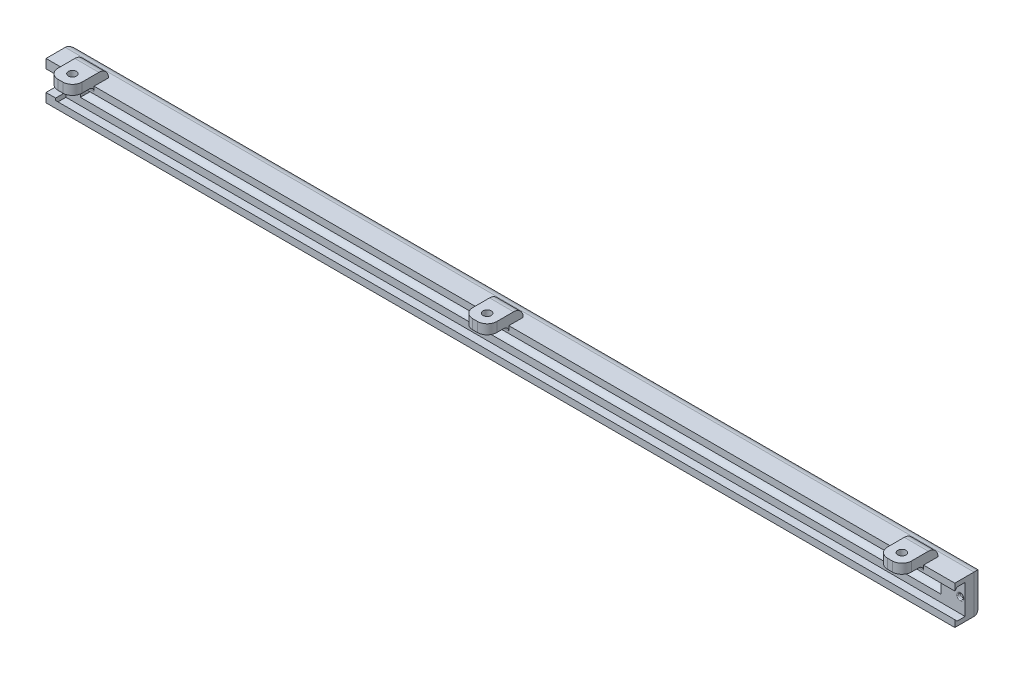
SolidWorks part; units mm, degrees
ref_plane "Front Plane" through (0, 0, 0) normal (0, 0, 1) x (1, 0, 0)
ref_plane "Top Plane" through (0, 0, 0) normal (0, 1, 0) x (1, 0, 0)
ref_plane "Right Plane" through (0, 0, 0) normal (1, 0, 0) x (0, 0, -1)
sketch "Sketch1" plane through (0, 0, 0) normal (0, 0, 1) x (1, 0, 0)
  line L1 (-157.5301, 47.1519) -> (220.4699, 47.1519)
  line L2 (-157.5301, 47.1519) -> (-157.5301, 31.1519)
  line L3 (-157.5301, 31.1519) -> (220.4699, 31.1519)
  line L4 (220.4699, 47.1519) -> (220.4699, 31.1519)
  dimension "D1" = 378
  dimension "D2" = 16
extrude "Boss-Extrude1" add sketch "Sketch1" along normal blind 6
sketch "Sketch3" plane through (220.4699, 0, 0) normal (1, 0, 0) x (0, 0, -1)
  line L0 (-6, 31.1519) -> (-6, 47.1519) construction
  line L1 (-6, 45.3019) -> (-1.7, 45.3019)
  line L2 (-6, 45.3019) -> (-6, 33.0019)
  line L3 (-6, 33.0019) -> (-1.7, 33.0019)
  line L4 (-1.7, 45.3019) -> (-1.7, 33.0019)
  line L5 (-6, 47.1519) -> (0, 47.1519) construction
  dimension "D1" = 12.3
  dimension "D2" = 4.3
  dimension "D3" = 1.85
extrude "Cut-Extrude1" cut sketch "Sketch3" against normal blind 374 and the other way through all
sketch "Sketch4" plane through (220.4699, 0, 0) normal (1, 0, 0) x (0, 0, -1)
  line L0 (-6, 33.0019) -> (-6, 34.0019)
  line L1 (-6, 45.3019) -> (-6, 33.0019) construction
  line L2 (-6, 34.0019) -> (-5, 33.0019)
  line L3 (-6, 33.0019) -> (-1.7, 33.0019) construction
  line L4 (-5, 33.0019) -> (-6, 33.0019)
  dimension "D1" = 1
  dimension "D2" = 1
extrude "Boss-Extrude2" add sketch "Sketch4" against normal blind 374
sketch "Sketch5" plane through (220.4699, 0, 0) normal (1, 0, 0) x (0, 0, -1)
  line L0 (-6, 45.3019) -> (-6, 44.3019)
  line L1 (-6, 45.3019) -> (-6, 34.0019) construction
  line L2 (-6, 44.3019) -> (-5, 45.3019)
  line L3 (-1.7, 45.3019) -> (-6, 45.3019) construction
  line L4 (-5, 45.3019) -> (-6, 45.3019)
  dimension "D1" = 1
  dimension "D2" = 1
extrude "Boss-Extrude3" add sketch "Sketch5" against normal blind 374
sketch "Sketch6" plane through (-153.5301, 0, 0) normal (1, 0, 0) x (0, 0, -1)
  line L0 (-6, 44.3019) -> (-6, 34.0019) construction
  line L1 (-6, 43.4019) -> (-2, 43.4019)
  line L2 (-6, 43.4019) -> (-6, 34.9019)
  line L3 (-6, 34.9019) -> (-2, 34.9019)
  line L4 (-2, 43.4019) -> (-2, 34.9019)
  line L5 (-6, 31.1519) -> (0, 31.1519) construction
  dimension "D1" = 8.5
  dimension "D2" = 3.75
  dimension "D3" = 4
extrude "Cut-Extrude2" cut sketch "Sketch6" against normal through all
sketch "Sketch13" plane through (0, 47.1519, 0) normal (0, 1, 0) x (1, 0, 0)
  line L0 (220.4699, 0) -> (-157.5301, 0) construction
  line L1 (-137.5301, 0) -> (-147.5301, 0)
  line L2 (-137.5301, 0) -> (-137.5301, -15)
  line L3 (-137.5301, -15) -> (-147.5301, -15)
  line L4 (-147.5301, 0) -> (-147.5301, -15)
  line L5 (-157.5301, -6) -> (-157.5301, 0) construction
  dimension "D1" = 10
  dimension "D2" = 10
  dimension "D3" = 15
extrude "Boss-Extrude5" add sketch "Sketch13" along normal blind 4
fillet "Fillet10" radius 4 1 edges at (-142.5301, 51.1519, 0)
sketch "Sketch14" plane through (0, 47.1519, 0) normal (0, -1, 0) x (1, 0, 0)
  line L1 (-147.5301, 0) -> (-157.5301, 0) construction
  circle A0 centre (-142.5301, 10) radius 1.7
  dimension "D1" = 3.4
  dimension "D2" = 10
extrude "Cut-Extrude5" cut sketch "Sketch14" against normal blind 4
fillet "Fillet11" radius 4 1 edges at (-137.5301, 49.1519, 15)
fillet "Fillet12" radius 4 1 edges at (-147.5301, 49.1519, 15)
pattern_linear "LPattern3" count 3 spacing 172.5 along (1, 0, 0) of "Boss-Extrude5"
pattern_linear "LPattern4" count 3 spacing 172.5 along (1, 0, 0) of "Cut-Extrude5"
fillet "Fillet13" radius 4 1 edges at (29.9699, 51.1519, 0)
fillet "Fillet14" radius 4 1 edges at (202.4699, 51.1519, 0)
fillet "Fillet16" radius 4 1 edges at (24.9699, 49.1519, 15)
fillet "Fillet17" radius 4 1 edges at (34.9699, 49.1519, 15)
fillet "Fillet18" radius 4 1 edges at (207.4699, 49.1519, 15)
fillet "Fillet19" radius 4 1 edges at (197.4699, 49.1519, 15)
fillet "Fillet20" radius 2 1 edges at (202.4699, 47.1519, 6)
fillet "Fillet21" radius 2 1 edges at (29.9699, 47.1519, 6)
fillet "Fillet22" radius 2 1 edges at (-142.5301, 47.1519, 6)
sketch "Sketch17" plane through (0, 0, 0) normal (0, 0, -1) x (-1, 0, 0)
  line L1 (-220.4699, 47.1519) -> (157.5301, 47.1519)
  line L2 (-220.4699, 47.1519) -> (-220.4699, 31.1519)
  line L3 (-220.4699, 31.1519) -> (157.5301, 31.1519)
  line L4 (157.5301, 47.1519) -> (157.5301, 31.1519)
extrude "Boss-Extrude6" add sketch "Sketch17" along normal blind 6
fillet "Fillet25" radius 4 4 edges at (31.4699, 47.1519, -6) (-157.5301, 39.1519, -6) (31.4699, 31.1519, -6) (220.4699, 39.1519, -6)
sketch "Sketch18" plane through (0, 0, 1.7) normal (0, 0, 1) x (1, 0, 0)
  line L0 (220.4699, 33.0019) -> (220.4699, 45.3019) construction
  line L1 (220.4699, 47.1519) -> (207.4699, 47.1519) construction
  circle A0 centre (218.4699, 39.1519) radius 1
  dimension "D3" = 2
  dimension "D1" = 2
  dimension "D2" = 8
extrude "Cut-Extrude6" cut sketch "Sketch18" against normal blind 0.7
fillet "Fillet26" radius 0.5 1 edges at (219.4699, 39.1519, 1.7)
fillet "Fillet27" radius 0.5 1 edges at (219.4699, 39.1519, 1)
sketch "Sketch19" plane through (0, 0, 1.7) normal (0, 0, 1) x (1, 0, 0)
  line L0 (-153.5301, 44.3019) -> (220.4699, 44.3019) construction
  line L1 (-147.5301, 42.3019) -> (210.4699, 42.3019)
  line L2 (-147.5301, 42.3019) -> (-147.5301, 36.0019)
  line L3 (-147.5301, 36.0019) -> (210.4699, 36.0019)
  line L4 (210.4699, 42.3019) -> (210.4699, 36.0019)
  line L5 (-153.5301, 34.0019) -> (220.4699, 34.0019) construction
  line L8 (-157.5301, 34.9019) -> (-157.5301, 43.4019) construction
  line L9 (220.4699, 33.0019) -> (220.4699, 45.3019) construction
  dimension "D1" = 2
  dimension "D2" = 2
  dimension "D3" = 10
  dimension "D4" = 10
extrude "Cut-Extrude7" cut sketch "Sketch19" against normal blind 3
fillet "Fillet28" radius 3 4 edges at (31.4699, 42.3019, -1.3) (210.4699, 39.1519, -1.3) (31.4699, 36.0019, -1.3) (-147.5301, 39.1519, -1.3)
